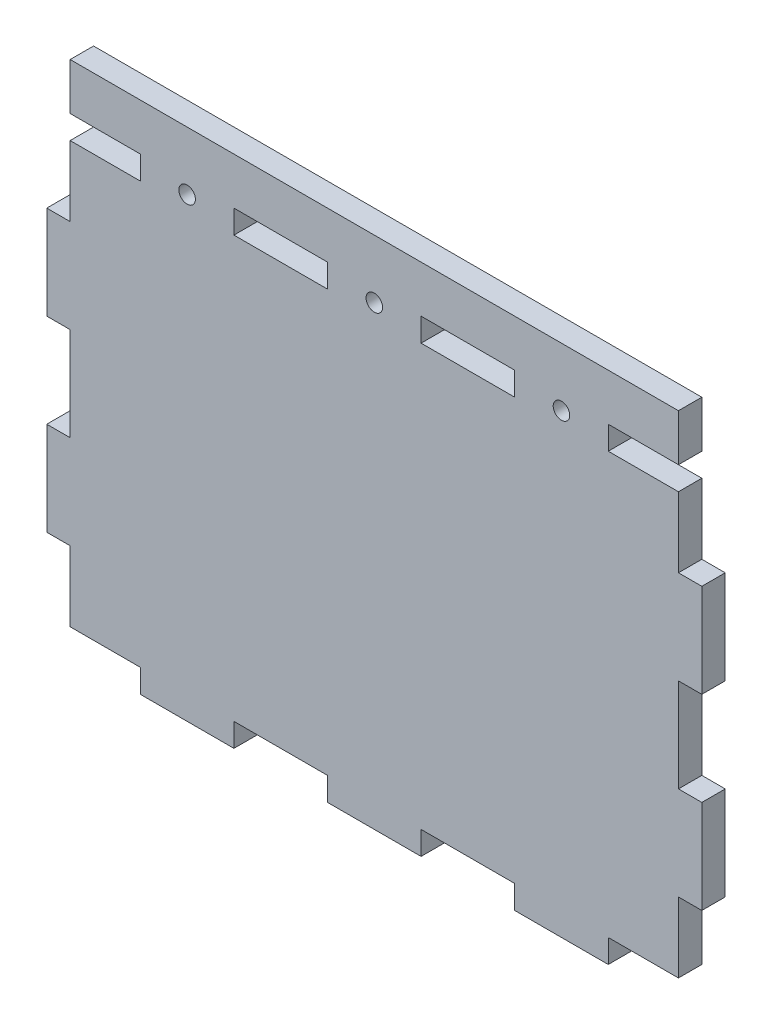
SolidWorks part; units mm, degrees
ref_plane "Front Plane" through (0, 0, 0) normal (0, 0, 1) x (1, 0, 0)
ref_plane "Top Plane" through (0, 0, 0) normal (0, 1, 0) x (1, 0, 0)
ref_plane "Right Plane" through (0, 0, 0) normal (1, 0, 0) x (0, 0, -1)
sketch "Sketch1" plane through (0, 0, 0) normal (0, 0, 1) x (1, 0, 0)
  line L1 (0, 0) -> (177.8, 0)
  line L2 (0, 0) -> (0, 139.7)
  line L3 (0, 139.7) -> (177.8, 139.7)
  line L4 (177.8, 0) -> (177.8, 139.7)
  dimension "D1" = 177.8
  dimension "D2" = 139.7
extrude "Boss-Extrude1" add sketch "Sketch1" along normal blind 6.35
sketch "Sketch5" plane through (0, 0, 6.35) normal (0, 0, 1) x (1, 0, 0)
  line L1 (0, 0) -> (6.35, 0)
  line L2 (0, 0) -> (0, 25.4)
  line L3 (0, 25.4) -> (6.35, 25.4)
  line L4 (6.35, 0) -> (6.35, 25.4)
  dimension "D1" = 25.4
  dimension "D2" = 6.35
extrude "Cut-Extrude4" cut sketch "Sketch5" against normal blind 6.35
sketch "Sketch6" plane through (0, 0, 6.35) normal (0, 0, 1) x (1, 0, 0)
  line L1 (0, 0) -> (25.4, 0)
  line L2 (0, 0) -> (0, 6.35)
  line L3 (0, 6.35) -> (25.4, 6.35)
  line L4 (25.4, 0) -> (25.4, 6.35)
  dimension "D1" = 6.35
  dimension "D2" = 25.4
extrude "Cut-Extrude5" cut sketch "Sketch6" against normal blind 6.35
pattern_linear "LPattern5" count 3 spacing 50.8 along (0, 1, 0) count 2 spacing 171.45 along (1, 0, 0) of "Cut-Extrude4"
pattern_linear "LPattern6" count 4 spacing 50.8 along (1, 0, 0) count 2 spacing 120.65 along (0, 1, 0) of "Cut-Extrude5"
sketch "Sketch7" plane through (0, 0, 6.35) normal (0, 0, 1) x (1, 0, 0)
  line L0 (177.8, 127) -> (152.4, 127) construction
  line L1 (6.35, 120.65) -> (0, 120.65)
  line L2 (6.35, 120.65) -> (6.35, 139.7)
  line L3 (6.35, 139.7) -> (0, 139.7)
  line L4 (0, 120.65) -> (0, 139.7)
  line L5 (177.8, 139.7) -> (171.45, 139.7)
  line L6 (177.8, 139.7) -> (177.8, 127)
  line L7 (177.8, 127) -> (171.45, 127)
  line L8 (171.45, 139.7) -> (171.45, 127)
  dimension "D1" = 6.35
  dimension "D2" = 19.05
  dimension "D3" = 6.35
extrude "Cut-Extrude6" cut sketch "Sketch7" against normal blind 6.35
hole_wizard "#8 Clearance Hole1" positions "Sketch10" profile "Sketch9" hole size "#8" standard "ANSI Inch"
sketch "Sketch10" plane through (0, 0, 6.35) normal (0, 0, 1) x (1, 0, 0)
  line L2 (25.4, 120.65) -> (25.4, 127) construction
  line L3 (76.2, 127) -> (50.8, 127) construction
  line L4 (76.2, 120.65) -> (76.2, 127) construction
  line L5 (127, 120.65) -> (127, 127) construction
  point P0 (38.1, 123.825)
  point P2 (88.9, 123.825)
  point P10 (25.4, 123.825)
  point P18 (139.7, 123.825)
  dimension "D1" = 12.7
  dimension "D2" = 12.7
  dimension "D3" = 12.7
  dimension "D4" = 3.175
sketch "Sketch9" plane through (38.1, 123.825, 6.35) normal (1, 0, 0) x (0, -1, 0)
  line L0 (0, 0) -> (0, 11.5107)
  line L1 (0, 11.5107) -> (2.2479, 10.16)
  line L2 (2.2479, 10.16) -> (2.2479, 0)
  line L5 (2.2479, 0) -> (0, 0)
  line L10 (0, 11.5107) -> (-2.2479, 10.16) construction
  line L11 (0, -6.35) -> (0, 107.95) construction
  dimension "Hole Dia." = 4.4958
  dimension "Hole Depth" = 10.16
  dimension "Drill Angle" = 118
